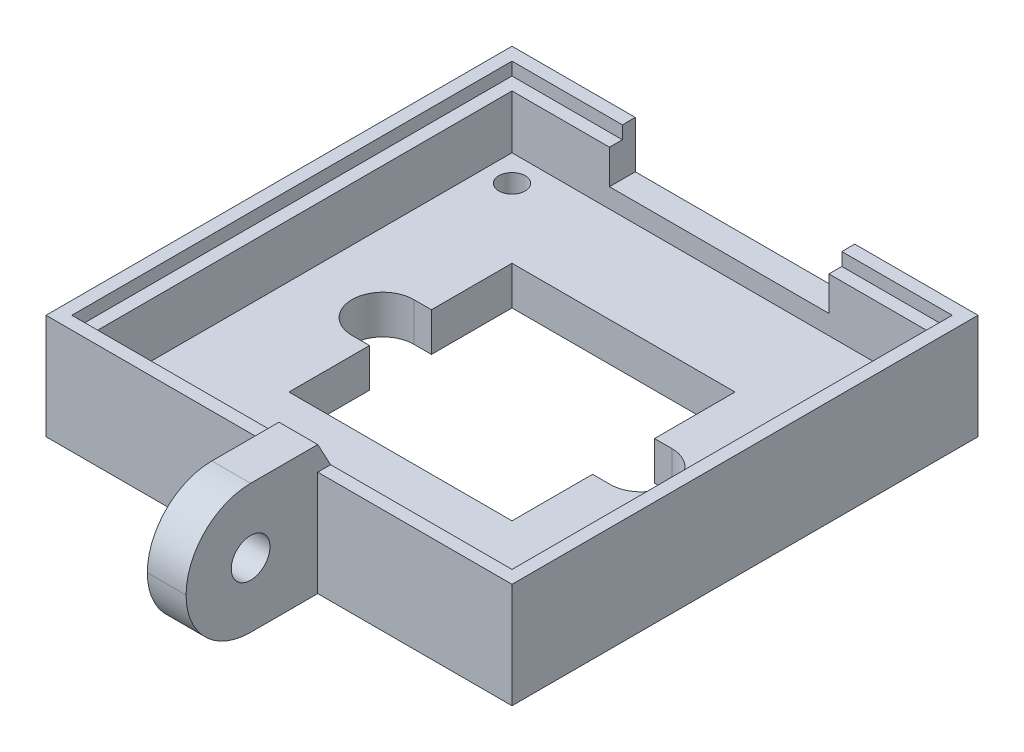
SolidWorks part; units mm, degrees
ref_plane "Front Plane" through (0, 0, 0) normal (0, 0, 1) x (1, 0, 0)
ref_plane "Top Plane" through (0, 0, 0) normal (0, 1, 0) x (1, 0, 0)
ref_plane "Right Plane" through (0, 0, 0) normal (1, 0, 0) x (0, 0, -1)
sketch "Sketch1" plane through (0, 0, 0) normal (0, 1, 0) x (1, 0, 0)
  line L0 (-10, 2.3) -> (-8.54, 2.3)
  line L1 (-16.05, -16.05) -> (16.05, -16.05)
  line L2 (-16.05, -16.05) -> (-16.05, 16.05)
  line L3 (-16.05, 16.05) -> (16.05, 16.05)
  line L4 (16.05, -16.05) -> (16.05, 16.05)
  line L5 (-16.05, -16.05) -> (16.05, 16.05) construction
  line L6 (-16.05, 16.05) -> (16.05, -16.05) construction
  line L7 (-8.54, -8.54) -> (8.54, -8.54)
  line L8 (-8.54, -8.54) -> (-8.54, -2.3)
  line L9 (-8.54, 8.54) -> (8.54, 8.54)
  line L10 (8.54, -8.54) -> (8.54, -2.3)
  line L11 (-8.54, -8.54) -> (8.54, 8.54) construction
  line L12 (-8.54, 8.54) -> (8.54, -8.54) construction
  line L13 (-10, -2.3) -> (-8.54, -2.3)
  line L14 (-8.54, 2.3) -> (-8.54, 8.54)
  line L15 (0, -8.54) -> (0, 8.54) construction
  line L16 (10, -2.3) -> (8.54, -2.3)
  line L17 (10, 2.3) -> (8.54, 2.3)
  line L18 (8.54, 2.3) -> (8.54, 8.54)
  line L19 (-8.64, 2.4) -> (-8.64, 8.64)
  line L20 (-8.64, 8.64) -> (8.64, 8.64)
  line L21 (8.64, 2.4) -> (8.64, 8.64)
  line L22 (10, 2.4) -> (8.64, 2.4)
  line L23 (10, -2.4) -> (8.64, -2.4)
  line L24 (8.64, -8.64) -> (8.64, -2.4)
  line L25 (-8.64, -8.64) -> (8.64, -8.64)
  line L26 (-8.64, -8.64) -> (-8.64, -2.4)
  line L27 (-10, -2.4) -> (-8.64, -2.4)
  line L28 (-10, 2.4) -> (-8.64, 2.4)
  line L33 (-18.05, -18.05) -> (-18.05, 18.05)
  line L34 (-18.05, 18.05) -> (18.05, 18.05)
  line L35 (18.05, -18.05) -> (18.05, 18.05)
  line L36 (-18.05, -18.05) -> (18.05, -18.05)
  circle A0 centre (-14, 14) radius 1.025
  circle A1 centre (14, 14) radius 1.025
  circle A2 centre (14, -14) radius 1.025
  circle A3 centre (-14, -14) radius 1.025
  circle A4 centre (-10, 0) radius 1
  circle A5 centre (10, 0) radius 1
  arc A6 (-10, 2.3) -> (-10, -2.3) centre (-10, 0) ccw
  arc A7 (10, 2.3) -> (10, -2.3) centre (10, 0) cw
  arc A8 (10, 2.4) -> (10, -2.4) centre (10, 0) cw
  arc A9 (-10, 2.4) -> (-10, -2.4) centre (-10, 0) ccw
  point P0 (0, 0)
  point P9 (0, 0)
  point P23 (-12.3, 0)
  dimension "D7" = 2
  dimension "D13" = 2.05
  dimension "D1" = 32.1
  dimension "D2" = 32.1
  dimension "D3" = 14
  dimension "D4" = 2
  dimension "D6" = 17.08
  dimension "D8" = 10
  dimension "D10" = 4.6
  dimension "D11" = 0.1
  dimension "D14" = 2
  dimension "D5" = 2
  dimension "D9" = 2
extrude "Boss-Extrude1" add sketch "Sketch1" along normal blind 3 contours L4 L1 L2 L3 | L1 L4 L3 L2 A9 L28 L19 L20 L21 L22 A8 L23 L24 L25 L26 L27 A0 A1 A2 A3 region at (-15.596, 0, 0) region at (-17.5395, 0, 0)
extrude "Boss-Extrude2" add sketch "Sketch1<3>" along normal blind 8.15 contours L33 L36 L35 L34 L4 L1 L2 L3
sketch "Sketch1<3>" plane through (0, 0, 0) normal (0, 1, 0) x (1, 0, 0) same geometry as "Sketch1"
sketch "Sketch2" plane through (0, 0, -18.05) normal (0, 0, -1) x (-1, 0, 0)
  line L1 (-8.5, 8.15) -> (8.5, 8.15)
  line L2 (-8.5, 8.15) -> (-8.5, 4.5)
  line L3 (-8.5, 4.5) -> (8.5, 4.5)
  line L4 (8.5, 8.15) -> (8.5, 4.5)
  line L6 (18.05, 0) -> (-18.05, 0) construction
  line L7 (18.05, 8.15) -> (-18.05, 8.15) construction
  point P6 (0, 4.5)
  dimension "D1" = 17
  dimension "D2" = 4.5
extrude "Cut-Extrude1" cut sketch "Sketch2" against normal blind 6
sketch "Sketch4" plane through (0, 8.15, 0) normal (0, 1, 0) x (1, 0, 0)
  line L27 (-16.05, -16.05) -> (16.05, -16.05) construction
  line L28 (16.05, -16.05) -> (16.05, 16.05) construction
  line L29 (8.5, 16.05) -> (16.05, 16.05) construction
  line L30 (8.5, 16.05) -> (8.5, 18.05) construction
  line L31 (-8.5, 18.05) -> (-8.5, 16.05) construction
  line L32 (17.05, -17.05) -> (-17.05, -17.05)
  line L33 (17.05, 17.05) -> (17.05, -17.05)
  line L34 (8.5, 17.05) -> (17.05, 17.05)
  line L35 (-17.05, 17.05) -> (-8.5, 17.05)
  line L36 (-17.05, -17.05) -> (-17.05, 17.05)
  line L37 (17.05, -17.05) -> (-17.05, -17.05)
  line L38 (17.05, 17.05) -> (17.05, -17.05)
  line L39 (8.5, 17.05) -> (17.05, 17.05)
  line L40 (-17.05, 17.05) -> (-8.5, 17.05)
  line L41 (-17.05, -17.05) -> (-17.05, 17.05)
  line L42 (-16.05, 16.05) -> (-8.5, 16.05) construction
  line L43 (-16.05, -16.05) -> (-16.05, 16.05) construction
  line L44 (-16.05, -16.05) -> (16.05, -16.05)
  line L45 (16.05, -16.05) -> (16.05, 16.05)
  line L46 (8.5, 16.05) -> (16.05, 16.05)
  line L47 (8.5, 16.05) -> (8.5, 17.05)
  line L48 (-8.5, 17.05) -> (-8.5, 16.05)
  line L49 (-16.05, 16.05) -> (-8.5, 16.05)
  line L50 (-16.05, -16.05) -> (-16.05, 16.05)
  dimension "D1" = 1
extrude "Cut-Extrude2" cut sketch "Sketch4" against normal blind 1
sketch "Sketch6" plane through (0, 0, 18.05) normal (0, 0, 1) x (1, 0, 0)
  line L1 (0, 0) -> (3, 0)
  line L2 (0, 0) -> (0, 10)
  line L3 (0, 10) -> (3, 10)
  line L4 (3, 0) -> (3, 10)
  dimension "D1" = 10
  dimension "D2" = 3
extrude "Boss-Extrude3" add sketch "Sketch6" along normal blind 10.2
fillet "Fillet1" radius 5 2 edges at (1.5, 0, 28.25) (1.5, 10, 28.25)
sketch "Sketch7" plane through (3, 0, 0) normal (1, 0, 0) x (0, 0, -1)
  circle A0 centre (-23.25, 5) radius 1.5
  dimension "D1" = 3
extrude "Cut-Extrude3" cut sketch "Sketch7" against normal blind 10
chamfer "Chamfer1" distance 1.85 distance2 1 1 edges at (1.5, 8.15, 18.05) first distance on face at (1.5, 9.075, 18.05)
